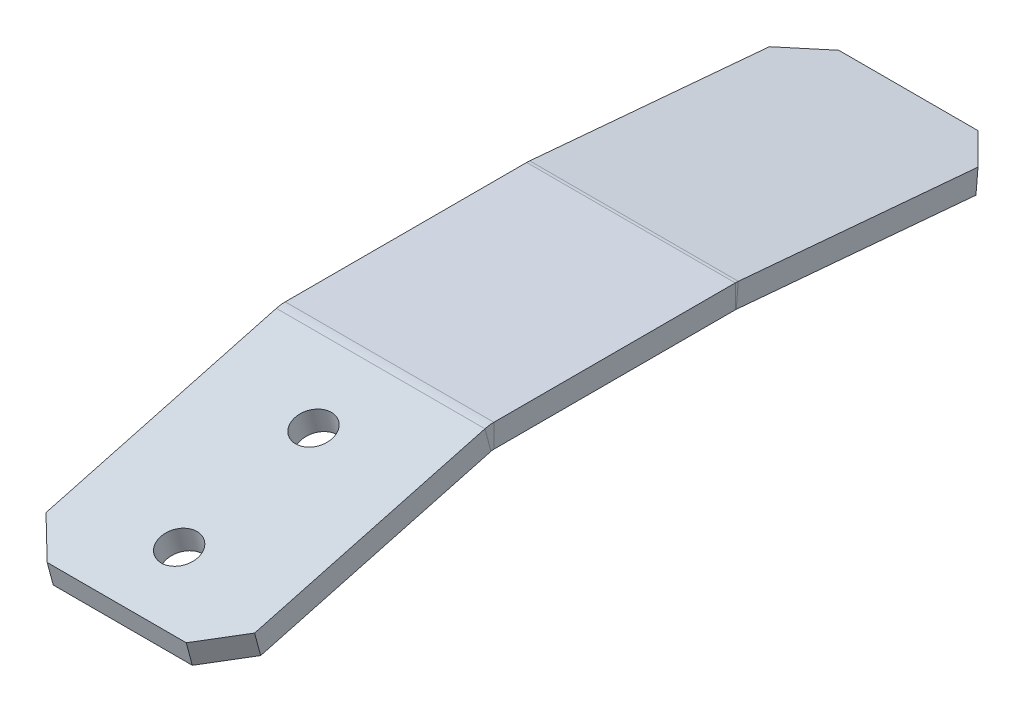
SolidWorks part; units mm, degrees
note: The reader was unsure of these and kept them because the rebuilt part matched: thickness of "Base-Flange1", "Edge-Flange1", "Edge-Flange2", "Sheet-Metal1", "Sheet-Metal2", "Sheet-Metal3", "Sheet-Metal4"; flange length of "Edge-Flange1", "Edge-Flange2".
ref_plane "Front Plane" through (0, 0, 0) normal (0, 0, 1) x (1, 0, 0)
ref_plane "Top Plane" through (0, 0, 0) normal (0, 1, 0) x (1, 0, 0)
ref_plane "Right Plane" through (0, 0, 0) normal (1, 0, 0) x (0, 0, -1)
sketch "Sketch1" plane through (0, 0, 0) normal (0, 1, 0) x (1, 0, 0)
  line L1 (19.05, -22.225) -> (-19.05, -22.225)
  line L3 (19.05, 22.225) -> (-19.05, 22.225)
  line L5 (19.05, -22.225) -> (-19.05, 22.225) construction
  line L6 (19.05, 22.225) -> (-19.05, -22.225) construction
  line L8 (-19.05, 22.225) -> (-19.05, -22.225)
  line L10 (19.05, 22.225) -> (19.05, -22.225)
  point P0 (0, 0)
  dimension "D1" = 38.1
  dimension "D2" = 44.45
base flange "Base-Flange1" sketch "Sketch1" thickness 4.2672 reverse thickness direction no parameters "D1"=2.032
edge flange "Edge-Flange1" sketch "Sketch8" flange angle 165 flange length 50.7348 flange position material outside bend radius 2.032 thickness 4.2672 relief rectangular parameters "D6"=10
sketch "Sketch8" plane through (0, -4.2672, 22.225) normal (0, 0.9659, 0.2588) x (-1, 0, 0)
  line L3 (-19.05, 50.173) -> (19.05, 50.173)
  line L11 (19.05, 0) -> (-19.05, 0) construction
  line L12 (19.05, 0) -> (-19.05, 0)
  line L13 (19.05, 0) -> (19.05, 50.173)
  line L14 (-19.05, 0) -> (-19.05, 50.173)
  line L15 (-19.05, -44.0398) -> (19.05, -44.0398) construction
  point P4 (0, -44.0398)
  dimension "D1" = 19.05
  dimension "D2" = 38.1
  dimension "D3" = 50.173
bend "EdgeBend1" bend radius 2.032 bend angle 15 parameters "D5"=1
edge flange "Edge-Flange2" sketch "Sketch11" flange angle 175 flange length 50.5696 flange position material outside bend radius 2.032 thickness 4.2672 relief rectangular parameters "D6"=10
sketch "Sketch11" plane through (0, -4.2672, -22.225) normal (0, 0.9962, -0.0872) x (1, 0, 0)
  line L3 (-19.05, 50.3833) -> (19.05, 50.3833)
  line L15 (19.05, 0) -> (-19.05, 0) construction
  line L16 (19.05, 0) -> (-19.05, 0)
  line L17 (-19.05, 50.3833) -> (-19.05, 0)
  line L18 (19.05, 50.3833) -> (19.05, 0)
  line L19 (-19.05, -44.3863) -> (19.05, -44.3863) construction
  point P4 (0, -44.3863)
  dimension "D1" = 19.05
  dimension "D2" = 38.1
  dimension "D3" = 50.3833
bend "EdgeBend2" bend radius 2.032 bend angle 5 parameters "D5"=2
chamfer "Chamfer1" distance 6.35 angle 45 4 edges at (-19.05, -15.192, 71.2406) (-19.05, -6.5329, -72.6026) (19.05, -6.5329, -72.6026) (19.05, -15.192, 71.2406)
hole_wizard "17/64 (0.26563) Diameter Hole1" positions "Sketch12" profile "Sketch13" hole size "17/64" standard "ANSI Inch" end condition through all
sketch "Sketch12" plane through (0, 5.6967, 1.5264) normal (0, 0.9659, 0.2588) x (1, 0, 0)
  line L1 (-12.7, -72.7451) -> (12.7, -72.7451) construction
  point P0 (0, -35.5397)
  point P2 (0, -60.9397)
  dimension "D1" = 25.4
  dimension "D2" = 11.8055
  dimension "D3" = 0
sketch "Sketch13" plane through (0, -3.5016, 35.8551) normal (1, 0, 0) x (0, -0.2588, 0.9659)
  line L0 (0, 0) -> (0, 41.4018)
  line L1 (0, 41.4018) -> (3.3735, 41.4018)
  line L2 (3.3735, 41.4018) -> (3.3735, 0)
  line L5 (3.3735, 0) -> (0, 0)
  line L11 (0, -6.35) -> (0, 107.95) construction
  dimension "Thru Hole Dia." = 6.747
  dimension "Thru Hole Depth" = 41.4018
sketch "Bend-Lines1" [suppressed] plane through (0, 0, 0) normal (0, 1, 0) x (1, 0, 0)
sketch "Bounding-Box1" [suppressed] plane through (0, 0, 0) normal (0, 1, 0) x (1, 0, 0)
sheet metal parameters "Sheet-Metal1" thickness 4.2672 parameters "D1"=2.032, "D7"=4.7625
flat pattern "Flat-Pattern1" [suppressed]
sketch "Bend-Lines2" plane through (0, 0, 0) normal (0, 1, 0) x (1, 0, 0)
sketch3d "Bounding-Box2" [suppressed]
  line L0 (477.8375, -22.225, 0) -> (7.9375, -22.225, 0) construction
  line L1 (477.8375, 22.225, 0) -> (7.9375, 22.225, 0) construction
  line L2 (477.8375, -22.225, 0) -> (477.8375, 22.225, 0) construction
  line L3 (7.9375, -22.225, 0) -> (7.9375, 22.225, 0) construction
sheet metal parameters "Sheet-Metal2" thickness 4.2672 parameters "D1"=2.032, "D7"=4.7625
flat pattern "Flat-Pattern1"
sketch "Bend-Lines2" plane through (0, 0, 0) normal (0, 1, 0) x (1, 0, 0)
  line L0 (-234.95, -22.5352) -> (234.95, -22.5352) construction
  line L1 (-234.95, -22.5352) -> (234.95, -22.5352) construction
sketch3d "Bounding-Box2" [suppressed]
  line L0 (477.8375, -73.0184, 0) -> (7.9375, -73.0184, 0) construction
  line L1 (477.8375, 22.225, 0) -> (7.9375, 22.225, 0) construction
  line L2 (477.8375, -73.0184, 0) -> (477.8375, 22.225, 0) construction
  line L3 (7.9375, -73.0184, 0) -> (7.9375, 22.225, 0) construction
bend of the flat pattern "Flatten-<EdgeBend1>1"
sheet metal parameters "Sheet-Metal3" thickness 4.2672 parameters "D1"=2.032, "D7"=4.7625
flat pattern "Flat-Pattern1"
sketch "Bend-Lines2" plane through (0, 0, 0) normal (0, 1, 0) x (1, 0, 0)
  line L0 (-236.5375, -22.5352) -> (236.5375, -22.5352) construction
  line L1 (-236.5375, -22.5352) -> (236.5375, -22.5352) construction
  line L2 (236.5375, 22.4324) -> (-236.5375, 22.4324) construction
  line L3 (236.5375, 22.4324) -> (-236.5375, 22.4324) construction
sketch3d "Bounding-Box2" [suppressed]
  line L0 (236.5375, 73.023, 0) -> (-236.5375, 73.023, 0) construction
  line L1 (236.5375, -73.0184, 0) -> (-236.5375, -73.0184, 0) construction
  line L2 (236.5375, 73.023, 0) -> (236.5375, -73.0184, 0) construction
  line L3 (-236.5375, 73.023, 0) -> (-236.5375, -73.0184, 0) construction
bend of the flat pattern "Flatten-<EdgeBend1>1"
bend of the flat pattern "Flatten-<EdgeBend2>1"
sheet metal parameters "Sheet-Metal4" thickness 4.2672 parameters "D1"=2.032, "D7"=4.7625
flat pattern "Flat-Pattern1"
sketch "Bend-Lines2" plane through (0, 0, 0) normal (0, 1, 0) x (1, 0, 0)
  line L0 (-19.05, -22.5028) -> (19.05, -22.5028) construction
  line L1 (-19.05, -22.5028) -> (19.05, -22.5028) construction
  line L2 (19.05, 22.318) -> (-19.05, 22.318) construction
  line L3 (19.05, 22.318) -> (-19.05, 22.318) construction
sketch3d "Bounding-Box2" [suppressed]
  line L0 (-19.05, -72.9535, 0) -> (-19.05, 72.7944, 0) construction
  line L1 (19.05, -72.9535, 0) -> (19.05, 72.7944, 0) construction
  line L2 (-19.05, -72.9535, 0) -> (19.05, -72.9535, 0) construction
  line L3 (-19.05, 72.7944, 0) -> (19.05, 72.7944, 0) construction
bend of the flat pattern "Flatten-<EdgeBend1>1"
bend of the flat pattern "Flatten-<EdgeBend2>1"
